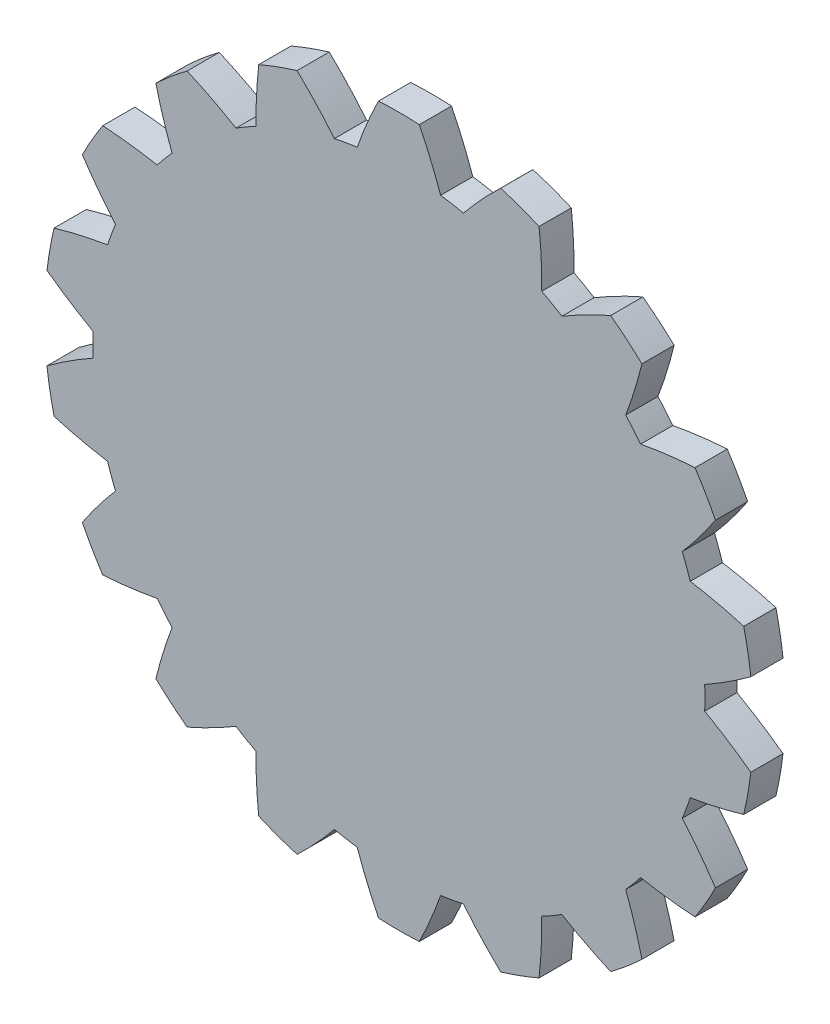
SolidWorks part; units mm, degrees
ref_plane "Front Plane" through (0, 0, 0) normal (0, 0, 1) x (1, 0, 0)
ref_plane "Top Plane" through (0, 0, 0) normal (0, 1, 0) x (1, 0, 0)
ref_plane "Right Plane" through (0, 0, 0) normal (1, 0, 0) x (0, 0, -1)
sketch "Sketch1" plane through (0, 0, 0) normal (0, 0, 1) x (1, 0, 0)
  circle A0 centre (0, 0) radius 55.88
  dimension "D1" = 111.76
extrude "Boss-Extrude1" add sketch "Sketch1" along normal blind 5.08
sketch "Sketch2" plane through (0, 0, 5.08) normal (0, 0, 1) x (1, 0, 0)
  line L0 (0, 0) -> (0, 55.88)
  line L1 (0, 0) -> (19.1121, 52.51)
  line L2 (0, 0) -> (9.7035, 55.0311)
  line L3 (0, 0) -> (27.94, 48.3935)
  line L4 (0, 0) -> (35.919, 42.8066)
  line L5 (0, 0) -> (42.8066, 35.919)
  line L6 (0, 0) -> (48.3935, 27.94)
  line L7 (0, 0) -> (52.51, 19.1121)
  line L8 (0, 0) -> (55.0311, 9.7035)
  line L9 (-55.88, 0) -> (55.88, 0)
  line L10 (0, 0) -> (55.0311, -9.7035)
  line L11 (0, 0) -> (52.51, -19.1121)
  line L12 (0, 0) -> (48.3935, -27.94)
  line L13 (0, 0) -> (42.8066, -35.919)
  line L14 (0, 0) -> (35.919, -42.8066)
  line L15 (0, 0) -> (27.94, -48.3935)
  line L16 (0, 0) -> (19.1121, -52.51)
  line L17 (0, 0) -> (9.7035, -55.0311)
  line L19 (0, 0) -> (-9.7035, -55.0311)
  line L20 (0, 0) -> (-19.1121, -52.51)
  line L21 (0, 0) -> (-27.94, -48.3935)
  line L22 (0, 0) -> (-35.919, -42.8066)
  line L23 (0, 0) -> (-42.8066, -35.919)
  line L24 (0, 0) -> (-48.3935, -27.94)
  line L25 (0, 0) -> (-52.51, -19.1121)
  line L26 (0, 0) -> (-55.0311, -9.7035)
  line L27 (0, 0) -> (-55.0311, 9.7035)
  line L28 (0, 0) -> (-52.51, 19.1121)
  line L29 (0, 0) -> (-48.3935, 27.94)
  line L30 (0, 0) -> (-42.8066, 35.919)
  line L31 (0, 0) -> (-35.919, 42.8066)
  line L32 (0, 0) -> (-27.94, 48.3935)
  line L33 (0, 0) -> (-9.7035, 55.0311)
  line L34 (0, 0) -> (-19.1121, 52.51)
  circle A0 centre (0, 0) radius 55.88 construction
  circle A1 centre (0, 0) radius 52.07
  circle A2 centre (0, 0) radius 48.26
  arc A3 (-6.5748, 47.81) -> (-3.2188, 55.7872) centre (59.5023, 24.7057) cw
  arc A4 (6.5748, 47.81) -> (3.2188, 55.7872) centre (-59.5023, 24.7057) ccw
  arc A5 (10.1737, 47.1755) -> (16.0557, 53.5237) centre (64.3637, 2.8647) cw
  arc A6 (22.5303, 42.678) -> (22.105, 51.322) centre (-47.4641, 43.5667) ccw
  arc A7 (25.6951, 40.8508) -> (33.3936, 44.8045) centre (61.4619, -19.3217) cw
  arc A8 (35.7683, 32.3984) -> (38.325, 40.6665) centre (-29.7009, 57.173) ccw
  arc A9 (38.1173, 29.599) -> (46.7038, 30.6811) centre (51.1469, -39.1777) cw
  arc A10 (38.1173, 29.599) -> (46.7038, 30.6811) centre (51.1469, -39.1777) cw
  arc A11 (44.6921, 18.2111) -> (49.9225, 25.1061) centre (-8.3554, 63.8834) ccw
  arc A12 (45.942, 14.777) -> (54.3808, 12.8572) centre (34.6628, -54.3083) cw
  arc A13 (45.942, 14.777) -> (54.3808, 12.8572) centre (34.6628, -54.3083) cw
  arc A14 (48.2254, 1.8272) -> (55.4986, 6.5175) centre (13.9979, 62.8885) ccw
  arc A15 (48.2254, -1.8272) -> (55.4986, -6.5175) centre (13.9979, -62.8885) cw
  arc A16 (45.942, -14.777) -> (54.3808, -12.8572) centre (34.6628, 54.3083) ccw
  arc A17 (44.6921, -18.2111) -> (49.9225, -25.1061) centre (-8.3554, -63.8834) cw
  arc A18 (38.1173, -29.599) -> (46.7038, -30.6811) centre (51.1469, 39.1777) ccw
  arc A19 (35.7683, -32.3984) -> (38.325, -40.6665) centre (-29.7009, -57.173) cw
  arc A20 (25.6951, -40.8508) -> (33.3936, -44.8045) centre (61.4619, 19.3217) ccw
  arc A21 (22.5303, -42.678) -> (22.105, -51.322) centre (-47.4641, -43.5667) cw
  arc A22 (10.1737, -47.1755) -> (16.0557, -53.5237) centre (64.3637, -2.8647) ccw
  arc A23 (6.5748, -47.81) -> (3.2188, -55.7872) centre (-59.5023, -24.7057) cw
  arc A24 (-6.5748, -47.81) -> (-3.2188, -55.7872) centre (59.5023, -24.7057) ccw
  arc A25 (-10.1737, -47.1755) -> (-16.0557, -53.5237) centre (-64.3637, -2.8647) cw
  arc A26 (-22.5303, -42.678) -> (-22.105, -51.322) centre (47.4641, -43.5667) ccw
  arc A27 (-25.6951, -40.8508) -> (-33.3936, -44.8045) centre (-61.4619, 19.3217) cw
  arc A28 (-35.7683, -32.3984) -> (-38.325, -40.6665) centre (29.7009, -57.173) ccw
  arc A29 (-38.1173, -29.599) -> (-46.7038, -30.6811) centre (-51.1469, 39.1777) cw
  arc A30 (-44.6921, -18.2111) -> (-49.9225, -25.1061) centre (8.3554, -63.8834) ccw
  arc A31 (-45.942, -14.777) -> (-54.3808, -12.8572) centre (-34.6628, 54.3083) cw
  arc A32 (-48.2254, -1.8272) -> (-55.4986, -6.5175) centre (-13.9979, -62.8885) ccw
  arc A33 (-48.2254, 1.8272) -> (-55.4986, 6.5175) centre (-13.9979, 62.8885) cw
  arc A34 (-45.942, 14.777) -> (-54.3808, 12.8572) centre (-34.6628, -54.3083) ccw
  arc A35 (-45.942, 14.777) -> (-54.3808, 12.8572) centre (-34.6628, -54.3083) ccw
  arc A36 (-44.6921, 18.2111) -> (-49.9225, 25.1061) centre (8.3554, 63.8834) cw
  arc A37 (-38.1173, 29.599) -> (-46.7038, 30.6811) centre (-51.1469, -39.1777) ccw
  arc A38 (-38.1173, 29.599) -> (-46.7038, 30.6811) centre (-51.1469, -39.1777) ccw
  arc A39 (-35.7683, 32.3984) -> (-38.325, 40.6665) centre (29.7009, 57.173) cw
  arc A40 (-25.6951, 40.8508) -> (-33.3936, 44.8045) centre (-61.4619, -19.3217) ccw
  arc A41 (-22.5303, 42.678) -> (-22.105, 51.322) centre (47.4641, 43.5667) cw
  arc A42 (-10.1737, 47.1755) -> (-16.0557, 53.5237) centre (-64.3637, 2.8647) ccw
  arc A43 (-6.5748, 47.81) -> (-3.2188, 55.7872) centre (59.5023, 24.7057) cw
  point P151 (0, 0)
  point P152 (0, 0)
  point P153 (3.2188, -55.88)
  point P154 (0, 0)
  point P155 (-3.2188, -55.88)
  circle M4 centre (0, 0) radius 55.88
  dimension "D3" = 7.62
  dimension "D4" = 3.81
  dimension "D5" = 70
  dimension "D1" = 20
  dimension "D2" = 10
  dimension "D6" = 19.2745
extrude "Cut-Extrude2" cut sketch "Sketch2" against normal blind 5.08 contours A4 A1 L2 M4 | A1 A5 L2 M4 | A2 A5 A1 L2 | A4 A2 L2 A1 region at (7.2421, 49.875, 5.08) region at (10.2529, 49.3441, 5.08) region at (6.7428, 53.6795, 5.08) region at (12.0233, 52.7484, 5.08)
extrude "Cut-Extrude3" cut sketch "Sketch2<8>" against normal blind 5.08 contours A6 A1 L3 M4 | A1 A7 L3 M4 | A2 A7 A1 L3 | A6 A2 L3 A1 | A8 A1 L5 M4 | A1 A9 L5 M4 | A2 A9 A1 L5 | A8 A2 L5 A1 | A11 A1 L7 M4 | A11 A2 L7 A1 | A1 A12 L7 M4 | A2 A12 A1 L7 | A14 A1 L9 M4 | A14 A2 L9 A1 | A1 A15 L9 M4 | A2 A15 A1 L9 | A16 A1 L11 M4 | A1 A17 L11 M4 | A16 A2 L11 A1 | A2 A17 A1 L11 | A18 A1 L13 M4 | A18 A2 L13 A1 | A2 A19 A1 L13 | A1 A19 L13 M4 | A20 A1 L15 M4 | A20 A2 L15 A1 | A2 A21 A1 L15 | A1 A21 L15 M4 | A22 A1 L17 M4 | A22 A2 L17 A1 | A2 A23 A1 L17 | A1 A23 L17 M4 region at (23.8636, 44.3902, 5.08) region at (26.5113, 42.8616, 5.08) region at (37.6068, 33.5514, 5.08) region at (39.572, 31.2093, 5.08) region at (46.814, 18.6657, 5.08) region at (47.8597, 15.7927, 5.08) region at (50.3749, 1.5287, 5.08) region at (50.3749, -1.5287, 5.08) region at (47.8597, -15.7927, 5.08) region at (46.814, -18.6657, 5.08) region at (39.572, -31.2093, 5.08) region at (37.6068, -33.5514, 5.08) region at (26.5113, -42.8616, 5.08) region at (23.8636, -44.3902, 5.08) region at (10.2529, -49.3441, 5.08) region at (7.2421, -49.875, 5.08) region at (24.6956, 48.136, 5.08) region at (29.3392, 45.455, 5.08) region at (39.6698, 36.7867, 5.08) region at (43.1164, 32.6792, 5.08) region at (49.8592, 21.0003, 5.08) region at (51.6931, 15.9617, 5.08) region at (54.0348, 2.681, 5.08) region at (54.0348, -2.681, 5.08) region at (51.6931, -15.9617, 5.08) region at (49.8592, -21.0003, 5.08) region at (43.1164, -32.6792, 5.08) region at (39.6698, -36.7867, 5.08) region at (29.3392, -45.455, 5.08) region at (24.6956, -48.136, 5.08) region at (12.0233, -52.7484, 5.08) region at (6.7428, -53.6795, 5.08)
sketch "Sketch2<8>" plane through (0, 0, 5.08) normal (0, 0, 1) x (1, 0, 0) same geometry as "Sketch2"
extrude "Cut-Extrude4" cut sketch "Sketch2<9>" against normal blind 5.08 contours A24 A1 L19 M4 | A24 A2 L19 A1 | A2 A25 A1 L19 | A1 A25 L19 M4 | A26 A1 L21 M4 | A26 A2 L21 A1 | A2 A27 A1 L21 | A1 A27 L21 M4 | A28 A1 L23 M4 | A28 A2 L23 A1 | A2 A29 A1 L23 | A1 A29 L23 M4 | A30 A2 L25 A1 | A30 A1 L25 M4 | A1 A31 L25 M4 | A2 A31 A1 L25 | A32 A2 L9 A1 | A32 A1 L9 M4 | A1 A33 L9 M4 | A2 A33 A1 L9 | A34 A1 L28 M4 | A34 A2 L28 A1 | A2 A36 A1 L28 | A1 A36 L28 M4 | A37 A1 L30 M4 | A37 A2 L30 A1 | A1 A39 L30 M4 | A2 A39 A1 L30 | A40 A1 L32 M4 | A40 A2 L32 A1 | A1 A41 L32 M4 | A2 A41 A1 L32 | A42 A1 L33 M4 | A1 A3 L33 M4 | A2 A3 A1 L33 | A42 A2 L33 A1 region at (-50.3749, -1.5287, 5.08) region at (-50.3749, 1.5287, 5.08) region at (-7.2421, -49.875, 5.08) region at (-10.2529, -49.3441, 5.08) region at (-23.8636, -44.3902, 5.08) region at (-26.5113, -42.8616, 5.08) region at (-37.6068, -33.5514, 5.08) region at (-39.572, -31.2093, 5.08) region at (-46.814, -18.6657, 5.08) region at (-47.8597, -15.7927, 5.08) region at (-47.8597, 15.7927, 5.08) region at (-46.814, 18.6657, 5.08) region at (-39.572, 31.2093, 5.08) region at (-37.6068, 33.5514, 5.08) region at (-26.5113, 42.8616, 5.08) region at (-23.8636, 44.3902, 5.08) region at (-10.2529, 49.3441, 5.08) region at (-7.2421, 49.875, 5.08) region at (-54.0348, -2.681, 5.08) region at (-54.0348, 2.681, 5.08) region at (-6.7428, -53.6795, 5.08) region at (-12.0233, -52.7484, 5.08) region at (-24.6956, -48.136, 5.08) region at (-29.3392, -45.455, 5.08) region at (-39.6698, -36.7867, 5.08) region at (-43.1164, -32.6792, 5.08) region at (-49.8592, -21.0003, 5.08) region at (-51.6931, -15.9617, 5.08) region at (-51.6931, 15.9617, 5.08) region at (-49.8592, 21.0003, 5.08) region at (-43.1164, 32.6792, 5.08) region at (-39.6698, 36.7867, 5.08) region at (-29.3392, 45.455, 5.08) region at (-24.6956, 48.136, 5.08) region at (-12.0233, 52.7484, 5.08) region at (-6.7428, 53.6795, 5.08)
sketch "Sketch2<9>" plane through (0, 0, 5.08) normal (0, 0, 1) x (1, 0, 0) same geometry as "Sketch2"
